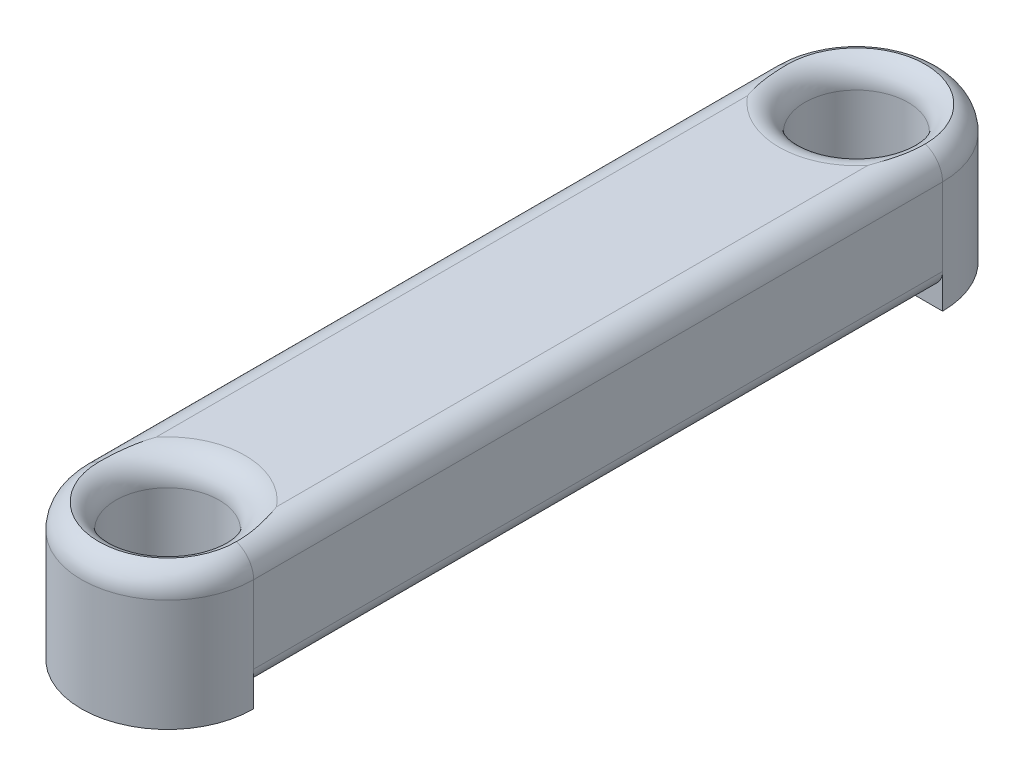
SolidWorks part; units mm, degrees
ref_plane "Front Plane" through (0, 0, 0) normal (0, 0, 1) x (1, 0, 0)
ref_plane "Top Plane" through (0, 0, 0) normal (0, 1, 0) x (1, 0, 0)
ref_plane "Right Plane" through (0, 0, 0) normal (1, 0, 0) x (0, 0, -1)
sketch "Sketch1" plane through (0, 0, 0) normal (0, 1, 0) x (1, 0, 0)
  line L0 (0, -10) -> (0, 10) construction
  line L1 (-2.5, -10) -> (-2.5, 10)
  line L2 (2.5, -10) -> (2.5, 10)
  arc A0 (-2.5, -10) -> (2.5, -10) centre (0, -10) ccw
  arc A1 (2.5, 10) -> (-2.5, 10) centre (0, 10) ccw
  circle A2 centre (0, -10) radius 1.5
  circle A3 centre (0, 10) radius 1.5
  point P2 (0, 0)
  dimension "D2" = 3
  dimension "D3" = 3
  dimension "D1" = 20
  dimension "D4" = 5
extrude "Boss-Extrude1" add sketch "Sketch1" along normal blind 4
sketch "Sketch2" plane through (2.5, 0, 0) normal (1, 0, 0) x (0, 0, -1)
  line L0 (10, 4) -> (10, 0) construction
  line L1 (-10, 0) -> (10, 0)
  line L2 (-10, 0) -> (-10, 0.5)
  line L3 (-10, 0.5) -> (10, 0.5)
  line L4 (10, 0) -> (10, 0.5)
  line L5 (-10, 0) -> (10, 0.5) construction
  line L6 (-10, 0.5) -> (10, 0) construction
  point P4 (0, 0.25)
  dimension "D1" = 0.5
extrude "Cut-Extrude1" cut sketch "Sketch2" against normal through all contours L3 L4 L1 L2
fillet "Fillet1" radius 0.5 2 edges at (-2.5, 0.5, 0) (2.5, 0.5, 0)
fillet "Fillet2" radius 0.75 6 edges at (0, 4, -8.5) (-2.5, 4, 0) (0, 4, -12.5) (2.5, 4, 0) (0, 4, 12.5) (0, 4, 11.5)
